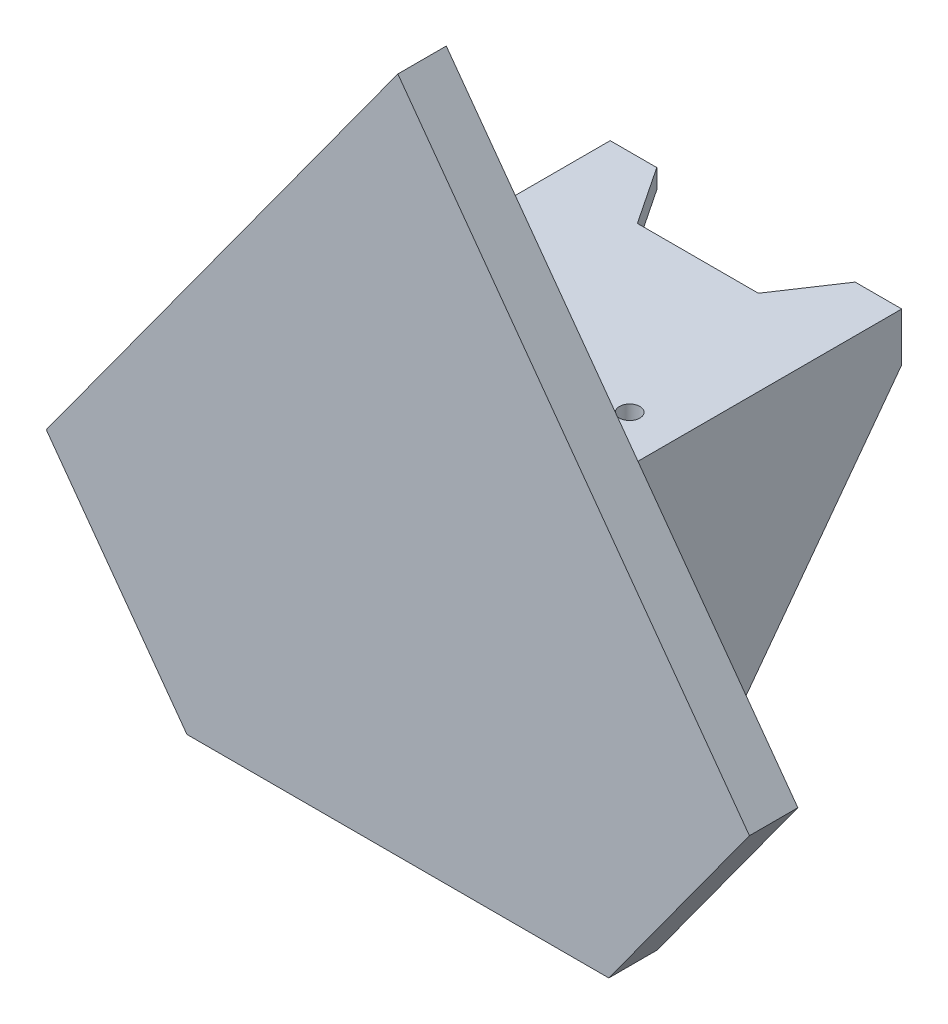
SolidWorks part; units mm, degrees
ref_plane "Front Plane" through (0, 0, 0) normal (0, 0, 1) x (1, 0, 0)
ref_plane "Top Plane" through (0, 0, 0) normal (0, 1, 0) x (1, 0, 0)
ref_plane "Right Plane" through (0, 0, 0) normal (1, 0, 0) x (0, 0, -1)
sketch "Sketch2" plane through (0, 0, 0) normal (0, 1, 0) x (1, 0, 0)
  line L0 (15.061, 0) -> (15.061, 32)
  line L1 (-12.561, 2.5) -> (12.561, 2.5)
  line L2 (-12.561, 2.5) -> (-12.561, 32)
  line L4 (12.561, 2.5) -> (12.561, 32)
  line L5 (15.061, 32) -> (12.561, 32)
  line L7 (-15.061, 32) -> (-15.061, 0)
  line L8 (-15.061, 0) -> (15.061, 0)
  line L10 (-15.061, 32) -> (-12.561, 32)
  point P4 (0, 2.5)
  point P12 (0, 0)
  dimension "D1" = 2.5
  dimension "D2" = 2.5
  dimension "D3" = 29.5
  dimension "D4" = 25.122
extrude "Boss-Extrude1" add sketch "Sketch2" along normal blind 32.5
sketch "Sketch4" plane through (0, 0, 0) normal (0, -1, 0) x (1, 0, 0)
  line L4 (-7.5, -6) -> (7.5, -6)
  line L9 (15.061, 0) -> (-15.061, 0)
  line L13 (-12.561, -2.5) -> (-12.561, -32) construction
  line L18 (-12.561, -10) -> (-7.5, -6)
  line L23 (12.561, -32) -> (12.561, -2.5) construction
  line L26 (12.561, -10) -> (7.5, -6)
  line L32 (-12.561, -10) -> (-15.061, -10)
  line L33 (-15.061, -32) -> (-15.061, 0) construction
  line L34 (-15.061, -10) -> (-15.061, 0)
  line L35 (12.561, -10) -> (15.061, -10)
  line L36 (15.061, 0) -> (15.061, -32) construction
  line L37 (15.061, -10) -> (15.061, 0)
  circle A2 centre (-10.2499, -4.95) radius 1.05
  circle A5 centre (10.2499, -4.95) radius 1.05
  point P31 (0, -6)
  dimension "D5" = 2.1
  dimension "D10" = 15
  dimension "D11" = 10
  dimension "D2" = 6
  dimension "D7" = 4.95
extrude "Boss-Extrude2" add sketch "Sketch4" along normal blind 1.5
sketch "Sketch5" plane through (0, 32.5, 0) normal (0, 1, 0) x (1, 0, 0)
  line L0 (-15.061, 32) -> (-10.2499, 32)
  line L9 (-10.2499, 32) -> (-6.25, 26)
  line L13 (-15.061, 0) -> (15.061, 0) construction
  line L14 (15.061, 0) -> (-15.061, 0)
  line L15 (-15.061, 0) -> (-15.061, 32)
  line L20 (15.061, 0) -> (15.061, 32)
  line L21 (-6.25, 26) -> (6.25, 26)
  line L22 (6.25, 26) -> (10.2499, 32)
  line L23 (10.2499, 32) -> (15.061, 32)
  circle A0 centre (-10.2499, 4.95) radius 1.05 construction
  circle A1 centre (-10.2499, 8.7) radius 1.05
  circle A2 centre (10.2499, 8.7) radius 1.05
  point P6 (0, 26)
  dimension "D4" = 0
  dimension "D1" = 8.7
  dimension "D2" = 12.5
  dimension "D3" = 20.4998
  dimension "D5" = 6
extrude "Boss-Extrude3" add sketch "Sketch5" along normal blind 2
sketch "Sketch6" plane through (-15.061, 0, 0) normal (-1, 0, 0) x (0, 0, 1)
  line L0 (-10, 0) -> (-32, 29.5)
  line L1 (-32, 29.5) -> (-32, 0)
  line L2 (-32, 0) -> (-10, 0)
  line L3 (-32, 34.5) -> (-32, 0) construction
  dimension "D1" = 5
extrude "Cut-Extrude1" cut sketch "Sketch6" against normal through all
ref_plane "Plane1" through (0, 16.5, 0) normal (0, -1, 0) x (-1, 0, 0)
sketch "Sketch8" plane through (0, 0, 0) normal (0, 0, 1) x (1, 0, 0)
  line L0 (0, 66.5) -> (36.3271, 16.5)
  line L1 (-16.5671, 16.5) -> (16.5671, 16.5) construction
  line L2 (36.3271, 16.5) -> (-36.3271, 16.5)
  line L3 (-36.3271, 16.5) -> (0, 66.5)
  dimension "D1" = 72
  dimension "D2" = 50
extrude "Boss-Extrude4" add sketch "Sketch8" along normal blind 5
sketch "Sketch9" plane through (0, 0, 0) normal (0, 0, 1) x (1, 0, 0)
  line L0 (-36.3271, 16.5) -> (-50.858, -3.5)
  line L1 (-50.858, -3.5) -> (50.858, -3.5)
  line L2 (50.858, -3.5) -> (36.3271, 16.5)
  line L3 (-36.3271, 16.5) -> (36.3271, 16.5)
  line L4 (0, 66.5) -> (-36.3271, 16.5) construction
  line L5 (36.3271, 16.5) -> (0, 66.5) construction
  dimension "D1" = 20
extrude "Boss-Extrude6" add sketch "Sketch9" along normal up to surface (5 mm away) up to face at (0, 33.1667, 5)
sketch "Sketch10" plane through (0, 0, 0) normal (0, 0, -1) x (-1, 0, 0)
  line L0 (-21.7963, -3.5) -> (-36.3271, 16.5)
  line L1 (50.858, -3.5) -> (-50.858, -3.5) construction
  line L2 (-50.858, -3.5) -> (0, 66.5) construction
  line L3 (-36.3271, 16.5) -> (-50.858, -3.5)
  line L4 (-50.858, -3.5) -> (-21.7963, -3.5)
  line L5 (50.858, -3.5) -> (36.3271, 16.5)
  line L13 (0, 66.5) -> (50.858, -3.5) construction
  line L14 (36.3271, 16.5) -> (21.7963, -3.5)
  line L15 (50.858, -3.5) -> (-50.858, -3.5) construction
  line L16 (21.7963, -3.5) -> (50.858, -3.5)
  point P13 (36.3271, -3.5)
  dimension "D1" = 20
extrude "Cut-Extrude2" cut sketch "Sketch10" against normal through all
